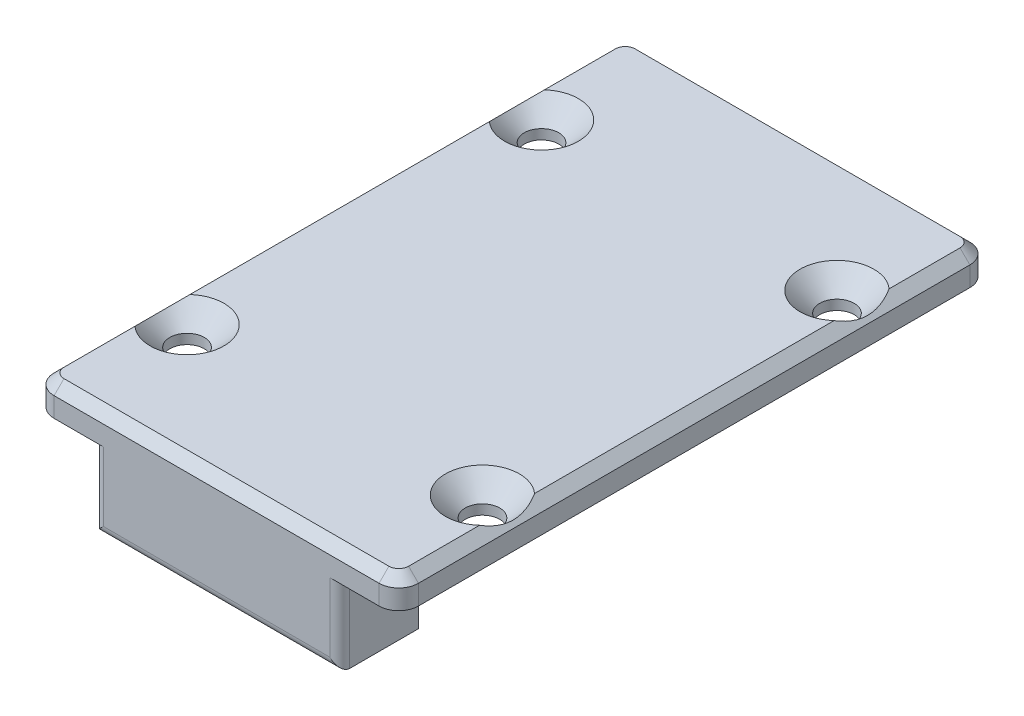
SolidWorks part; units mm, degrees
ref_plane "Спереди" through (0, 0, 0) normal (0, 0, 1) x (1, 0, 0)
ref_plane "Сверху" through (0, 0, 0) normal (0, 1, 0) x (1, 0, 0)
ref_plane "Справа" through (0, 0, 0) normal (1, 0, 0) x (0, 0, -1)
sketch "Эскиз1" plane through (0, 0, 0) normal (0, 1, 0) x (1, 0, 0)
  line L1 (-18.5, -30) -> (18.5, -30)
  line L2 (-18.5, -30) -> (-18.5, 30)
  line L3 (-18.5, 30) -> (18.5, 30)
  line L4 (18.5, -30) -> (18.5, 30)
  line L5 (0, 30) -> (0, -30) construction
  line L6 (-18.5, 0) -> (18.5, 0) construction
  point P0 (0, 0)
  dimension "D1" = 60
  dimension "D2" = 37
extrude "Бобышка-Вытянуть1" add sketch "Эскиз1" along normal blind 3
sketch "Эскиз2" plane through (0, 3, 0) normal (0, 1, 0) x (1, 0, 0)
  line L0 (0, 32.2776) -> (0, 0) construction
  line L1 (0, 0) -> (26.8846, 0) construction
  line L2 (18.5, -30) -> (18.5, 30) construction
  circle A0 centre (15, 18) radius 1.75
  circle A1 centre (15, -18) radius 1.75
  circle A2 centre (-15, -18) radius 1.75
  circle A3 centre (-15, 18) radius 1.75
  dimension "D1" = 18
  dimension "D2" = 3.5
  dimension "D3" = 3.5
extrude "Вырез-Вытянуть1" cut sketch "Эскиз2" against normal blind 3
fillet "Скругление1" radius 2 4 edges at (18.5, 1.5, -30) (-18.5, 1.5, -30) (-18.5, 1.5, 30) (18.5, 1.5, 30)
sketch "Эскиз3" plane through (0, 0, 0) normal (0, -1, 0) x (1, 0, 0)
  line L0 (0, 32.2375) -> (0, 0) construction
  line L1 (0, 0) -> (33.8614, 0) construction
  line L2 (-16.5, 30) -> (16.5, 30) construction
  line L3 (-12.5, 22) -> (12.5, 22)
  line L4 (-12.5, 22) -> (-12.5, 30)
  line L5 (-12.5, 30) -> (12.5, 30)
  line L6 (12.5, 22) -> (12.5, 30)
  line L7 (0, 30) -> (0, 22) construction
  line L8 (-12.5, 26) -> (12.5, 26) construction
  point P3 (0, 26)
  dimension "D1" = 25
  dimension "D2" = 8
extrude "Бобышка-Вытянуть2" add sketch "Эскиз3" along normal blind 8
fillet "Скругление2" radius 1 3 edges at (-12.5, -4, 30) (0, -8, 30) (12.5, -4, 30)
chamfer "Фаска2" distance 1 angle 45 8 edges at (-18.5, 3, 0) (17.9142, 3, -29.4142) (-17.9142, 3, -29.4142) (0, 3, -30) (-17.9142, 3, 29.4142) (0, 3, 30) (17.9142, 3, 29.4142) (18.5, 3, 0)
chamfer "Фаска1" distance 2 angle 45 4 edges at (-15, 3, 19.75) (15, 3, 16.25) (-15, 3, -19.75) (15, 3, -16.25)
